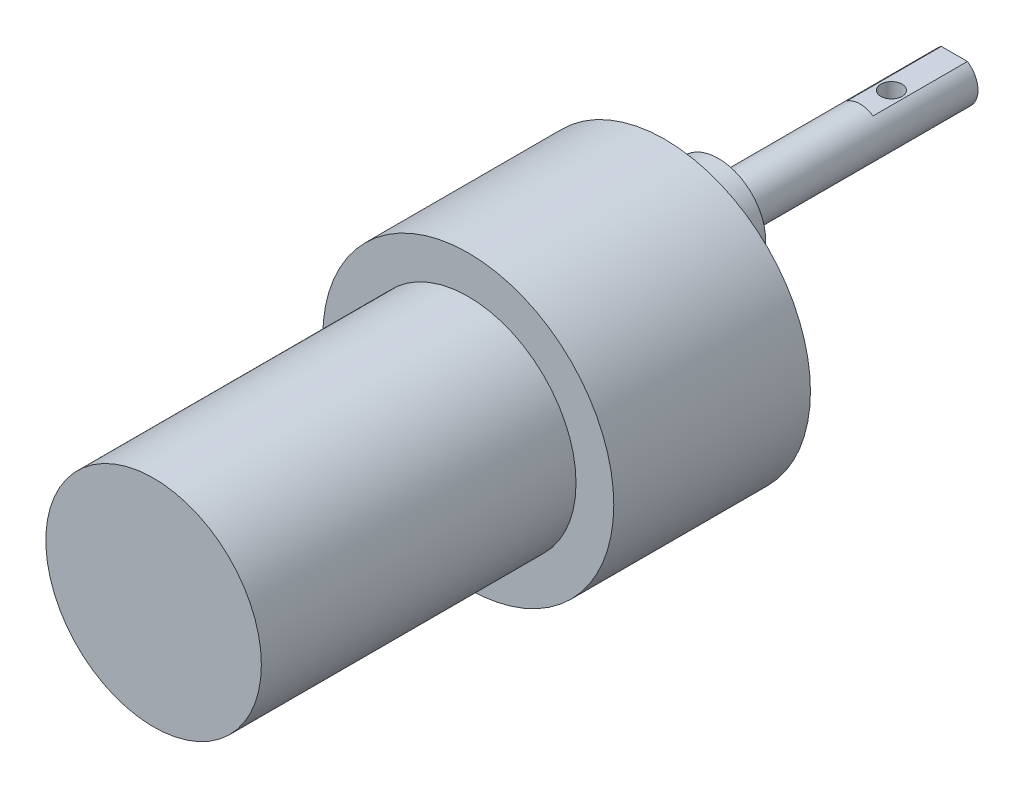
SolidWorks part; units mm, degrees
material "Plain Carbon Steel"
ref_plane "Front Plane" through (0, 0, 0) normal (0, 0, 1) x (1, 0, 0)
ref_plane "Top Plane" through (0, 0, 0) normal (0, 1, 0) x (1, 0, 0)
ref_plane "Right Plane" through (0, 0, 0) normal (1, 0, 0) x (0, 0, -1)
sketch "Sketch1" plane through (0, 0, 0) normal (0, 0, 1) x (1, 0, 0)
  circle A0 centre (0, 0) radius 18.5
  dimension "D1" = 37
extrude "Boss-Extrude1" add sketch "Sketch1" along normal blind 25
sketch "Sketch2" plane through (0, 0, 0) normal (0, 0, -1) x (-1, 0, 0)
  circle A0 centre (0, 7) radius 6
  dimension "D1" = 12
  dimension "D2" = 7
extrude "Boss-Extrude2" add sketch "Sketch2" along normal blind 6.8
sketch "Sketch3" plane through (0, 0, -6.8) normal (0, 0, -1) x (-1, 0, 0)
  circle A0 centre (0, 7) radius 3
extrude "Boss-Extrude3" add sketch "Sketch3" along normal blind 30
sketch "Sketch4" plane through (0, 0, -36.8) normal (0, 0, -1) x (-1, 0, 0)
  line L0 (-1.6583, 9.5) -> (1.6583, 9.5)
  circle A0 centre (0, 7) radius 3
  circle M2 centre (0, 7) radius 3
  dimension "D1" = 2.5
  dimension "D2" = 6
extrude "Cut-Extrude1" cut sketch "Sketch4" against normal blind 12 contours L0 M2 region at (0, 9.7015, -36.8)
sketch "Sketch5" plane through (0, 0, 25) normal (0, 0, 1) x (1, 0, 0)
  circle A0 centre (0, 0) radius 13.7
  dimension "D1" = 27.4
extrude "Boss-Extrude4" add sketch "Sketch5" along normal blind 40
sketch "Sketch6" plane through (0, 0, 0) normal (0, 0, -1) x (-1, 0, 0)
  line L0 (0, 7) -> (0, 0) construction
  line L1 (0, 0) -> (-15.75, 0) construction
  circle A0 centre (0, 0) radius 15.75 construction
  circle A1 centre (-15.75, 0) radius 1.5
  circle A2 centre (-7.875, 13.6399) radius 1.5
  circle A3 centre (7.875, 13.6399) radius 1.5
  circle A4 centre (15.75, 0) radius 1.5
  circle A5 centre (7.875, -13.6399) radius 1.5
  circle A6 centre (-7.875, -13.6399) radius 1.5
  point P19 (0, 0)
  dimension "D1" = 31.5
  dimension "D2" = 3
  dimension "D3" = 6
extrude "Cut-Extrude2" cut sketch "Sketch6" against normal blind 3.2
thread "Thread1" pitch 1.0583 method extrude profile "Thread Profile1" start angle 0, offset 0, length 3.2, pitch 1.0583, diameter 3
ref_plane "Plane1" through (17.25, 0, 0) normal (0, -1, 0) x (1, 0, 0)
sketch "Thread Profile1" plane through (17.25, 0, 0) normal (0, -1, 0) x (1, 0, 0)
  line L0 (0, 0) -> (0, 1.0583) construction
  line L11 (0, 0) -> (0, 0.926)
  line L12 (0, 0.926) -> (-0.5728, 0.5953)
  line L13 (-0.5728, 0.5953) -> (-0.5728, 0.3307)
  line L15 (-0.5728, 0.3307) -> (0, 0)
  line L17 (-0.5728, 0.463) -> (0, 0.463) construction
  point P2 (0, 0)
  dimension "Pitch" = 1.0583
  dimension "Profile_Angle" = 60
  dimension "Profile_Land" = 0.2646
  dimension "Profile_Height" = 0.5728
sketch "Sketch7" plane through (0, 9.5, 0) normal (0, 1, 0) x (1, 0, 0)
  line L0 (1.6583, 36.8) -> (-1.6583, 36.8) construction
  circle A0 centre (0, 28.8) radius 1.3505
  dimension "D1" = 8
extrude "Cut-Extrude3" cut sketch "Sketch7" against normal blind 10
